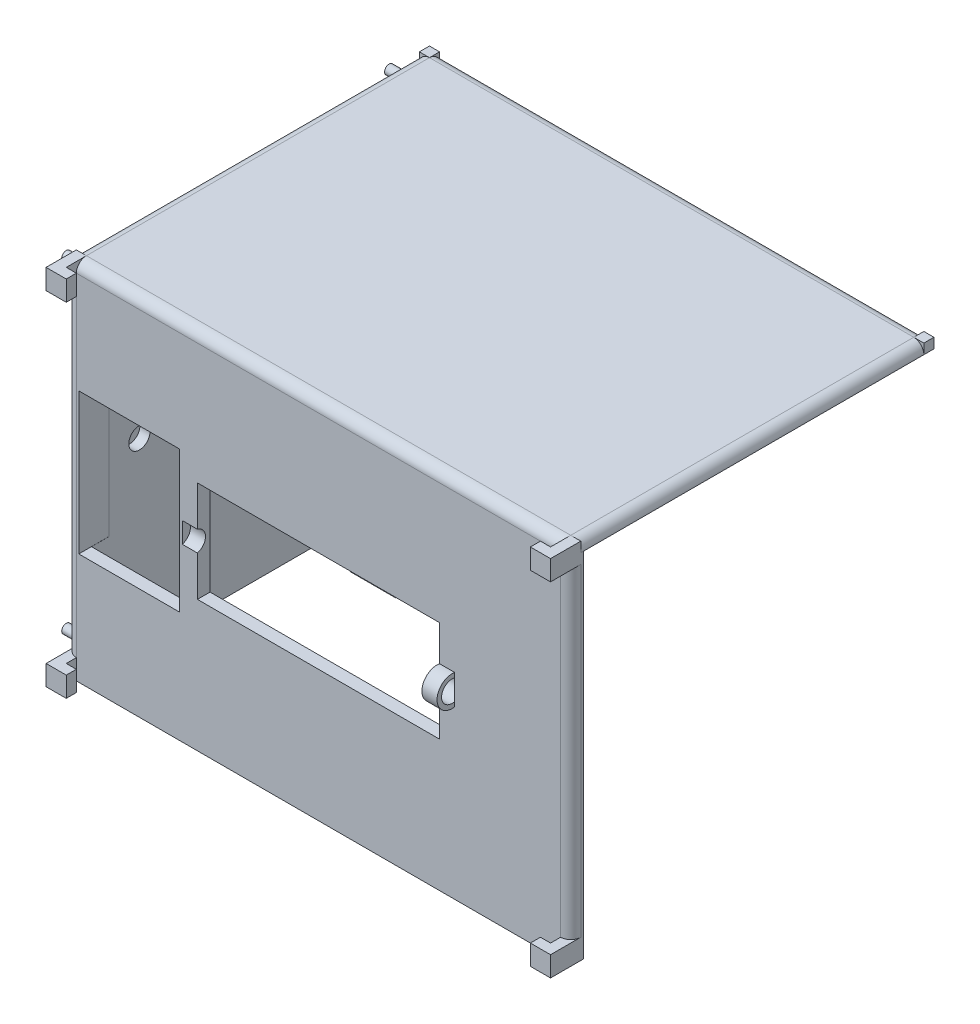
SolidWorks part; units mm, degrees
ref_plane "Front Plane" through (0, 0, 0) normal (0, 0, 1) x (1, 0, 0)
ref_plane "Top Plane" through (0, 0, 0) normal (0, 1, 0) x (1, 0, 0)
ref_plane "Right Plane" through (0, 0, 0) normal (1, 0, 0) x (0, 0, -1)
sketch "Sketch1" plane through (0, 0, 0) normal (0, 1, 0) x (1, 0, 0)
  line L1 (-63.5, -45.72) -> (63.5, -45.72)
  line L2 (-63.5, -45.72) -> (-63.5, 45.72)
  line L3 (-63.5, 45.72) -> (63.5, 45.72)
  line L4 (63.5, -45.72) -> (63.5, 45.72)
  line L5 (-63.5, -45.72) -> (63.5, 45.72) construction
  line L6 (-63.5, 45.72) -> (63.5, -45.72) construction
  point P0 (0, 0)
  dimension "D1" = 91.44
  dimension "D2" = 127
extrude "Boss-Extrude1" add sketch "Sketch1" along normal blind 228.6
sketch "Sketch2" plane through (63.5, 0, 0) normal (1, 0, 0) x (0, 0, -1)
  line L1 (-45.72, 137.16) -> (45.72, 137.16) construction
  line L2 (-45.72, 137.16) -> (-45.72, 228.6) construction
  line L3 (-45.72, 228.6) -> (45.72, 228.6) construction
  line L4 (45.72, 137.16) -> (45.72, 228.6) construction
  line L5 (-45.72, 137.16) -> (45.72, 228.6) construction
  line L6 (-45.72, 228.6) -> (45.72, 137.16) construction
  circle A0 centre (0, 182.88) radius 2.667
  point P0 (0, 182.88)
  dimension "D2" = 5.334
  dimension "D1" = 91.44
sketch "Sketch3" plane through (0, 0, 0) normal (0, -1, 0) x (1, 0, 0)
  line L0 (63.5, 45.72) -> (63.5, -45.72) construction
  line L1 (-60.325, -42.545) -> (60.325, -42.545)
  line L2 (-60.325, -42.545) -> (-60.325, 42.545)
  line L3 (-60.325, 42.545) -> (60.325, 42.545)
  line L4 (60.325, -42.545) -> (60.325, 42.545)
  line L5 (-60.325, -42.545) -> (60.325, 42.545) construction
  line L6 (-60.325, 42.545) -> (60.325, -42.545) construction
  line L7 (-63.5, 45.72) -> (63.5, 45.72) construction
  point P0 (0, 0)
  dimension "D1" = 3.175
  dimension "D2" = 3.175
extrude "Cut-Extrude1" cut sketch "Sketch3" against normal blind 226.06
extrude "Cut-Extrude2" cut sketch "Sketch2" against normal through all contours A0
sketch "Sketch4" plane through (63.5, 0, 0) normal (1, 0, 0) x (0, 0, -1)
  line L3 (-45.72, 228.6) -> (45.72, 228.6) construction
  circle A0 centre (-40.64, 223.52) radius 1.143
  circle A1 centre (40.64, 223.52) radius 1.143
  circle A2 centre (40.64, 142.24) radius 1.143
  circle A3 centre (-40.64, 142.24) radius 1.143
  point P0 (0, 182.88)
  dimension "D7" = 2.286
extrude "Boss-Extrude3" add sketch "Sketch4" along normal blind 5.08
sketch "Sketch5" plane through (60.325, 0, 0) normal (-1, 0, 0) x (0, 0, 1)
  circle A0 centre (0, 182.88) radius 20.32
  dimension "D1" = 40.64
extrude "Cut-Extrude3" cut sketch "Sketch5" against normal blind 1.27
fillet "Fillet1" radius 0.762 1 edges at (61.595, 182.88, 2.667)
fillet "Fillet2" radius 0.762 1 edges at (63.5, 182.88, -2.667)
sketch "Sketch6" plane through (0, 0, 45.72) normal (0, 0, 1) x (1, 0, 0)
  line L0 (0, 0) -> (0, 228.6) construction
  line L1 (-63.5, 228.6) -> (63.5, 228.6) construction
  line L3 (2.7526, 228.6) -> (2.7526, 182.88) construction
  line L4 (-30.48, 170.18) -> (30.48, 170.18)
  line L5 (30.48, 170.18) -> (30.48, 195.58)
  line L6 (-30.48, 170.18) -> (-30.48, 195.58)
  line L7 (30.48, 195.58) -> (-30.48, 195.58)
  line L8 (-30.48, 182.88) -> (30.48, 182.88) construction
  point P10 (0, 170.18)
  dimension "D1" = 45.72
  dimension "D2" = 60.96
  dimension "D3" = 25.4
mirror "Mirror2" about plane through (0, 0, 0) normal (1, 0, 0) of "Cut-Extrude3", "Boss-Extrude3"
fillet "Fillet3" radius 0.762 2 edges at (-61.595, 182.88, -2.667) (-63.5, 182.88, -2.667)
extrude "Cut-Extrude4" cut sketch "Sketch6" against normal through all
fillet "Fillet4" radius 2.54 8 edges at (63.5, 228.6, 0) (0, 228.6, 45.72) (0, 228.6, -45.72) (-63.5, 228.6, 0) (-63.5, 114.3, -45.72) (-63.5, 114.3, 45.72) (63.5, 114.3, 45.72) (63.5, 114.3, -45.72)
sketch "Sketch7" plane through (63.5, 0, 0) normal (1, 0, 0) x (0, 0, -1)
  line L0 (45.72, 226.06) -> (45.72, 0) construction
  line L1 (-42.545, 20.32) -> (42.545, 20.32)
  line L2 (-42.545, 20.32) -> (-42.545, 131.4726)
  line L3 (-42.545, 131.4726) -> (42.545, 131.4726)
  line L4 (42.545, 20.32) -> (42.545, 131.4726)
  line L5 (-42.545, 20.32) -> (42.545, 131.4726) construction
  line L6 (-42.545, 131.4726) -> (42.545, 20.32) construction
  line L7 (-45.72, 0) -> (-45.72, 226.06) construction
  line L8 (-43.18, 0) -> (43.18, 0) construction
  point P0 (0, 75.8963)
  dimension "D1" = 3.175
  dimension "D2" = 3.175
  dimension "D3" = 20.32
extrude "Cut-Extrude5" cut sketch "Sketch7" against normal through all
sketch "Sketch10" plane through (60.325, 0, 0) normal (-1, 0, 0) x (0, 0, 1)
  line L0 (0, 182.88) -> (-30.48, 182.88) construction
  line L1 (-43.18, 226.06) -> (43.18, 226.06) construction
  circle A0 centre (-30.48, 182.88) radius 2.667
  dimension "D2" = 5.334
  dimension "D1" = 30.48
extrude "Cut-Extrude6" cut sketch "Sketch10" against normal blind 2.54
sketch "Sketch11" plane through (60.325, 0, 0) normal (-1, 0, 0) x (0, 0, 1)
  line L0 (-30.48, 182.88) -> (-45.72, 182.88) construction
  dimension "D1" = 15.24
sketch "Sketch12" plane through (0, 0, -45.72) normal (0, 0, -1) x (-1, 0, 0)
  line L1 (-34.8104, 182.8079) -> (-34.8104, 200.5879)
  line L2 (-34.8104, 182.8079) -> (-34.8104, 165.0279)
  line L3 (-34.8104, 165.0279) -> (-60.2104, 165.0279)
  line L4 (-60.2104, 165.0279) -> (-60.2104, 182.8079)
  line L5 (-34.8104, 200.5879) -> (-60.2104, 200.5879)
  line L6 (-60.2104, 200.5879) -> (-60.2104, 182.8079)
  dimension "D1" = 25.4
  dimension "D2" = 17.78
  dimension "D3" = 35.56
extrude "Cut-Extrude7" cut sketch "Sketch12" against normal blind 7.62
sketch "Sketch13" plane through (-60.325, 0, 0) normal (1, 0, 0) x (0, 0, -1)
  line L0 (0, 182.88) -> (-30.48, 182.88) construction
  circle A0 centre (-30.48, 182.88) radius 2.667
  dimension "D2" = 5.334
  dimension "D1" = 30.48
extrude "Cut-Extrude8" cut sketch "Sketch13" against normal blind 2.54
sketch "Sketch15" plane through (-60.325, 0, 0) normal (1, 0, 0) x (0, 0, -1)
  line L0 (-30.48, 182.88) -> (-45.72, 182.88) construction
  dimension "D1" = 15.24
sketch "Sketch16" plane through (0, 0, 45.72) normal (0, 0, 1) x (1, 0, 0)
  line L0 (-60.3464, 182.9342) -> (-60.3464, 200.7142)
  line L1 (-60.3464, 182.9342) -> (-60.3464, 165.1542)
  line L2 (-60.3464, 165.1542) -> (-34.9464, 165.1542)
  line L3 (-34.9464, 165.1542) -> (-34.9464, 200.7142)
  line L4 (-34.9464, 200.7142) -> (-60.3464, 200.7142)
  dimension "D1" = 17.78
  dimension "D2" = 17.78
  dimension "D3" = 25.4
extrude "Cut-Extrude9" cut sketch "Sketch16" against normal blind 7.62
sketch "Sketch17" plane through (-63.5, 0, 0) normal (-1, 0, 0) x (0, 0, 1)
sketch "Sketch20" plane through (0, 226.06, 0) normal (0, -1, 0) x (1, 0, 0)
  line L0 (62.865, -30.48) -> (-4.445, -30.48) construction
  line L1 (62.865, -27.813) -> (62.865, -33.147) construction
  line L2 (-4.445, -30.48) -> (6.985, -30.48) construction
  line L3 (6.985, -34.29) -> (6.985, -26.67)
  line L4 (6.985, -34.29) -> (-4.445, -34.29)
  line L5 (-4.445, -34.29) -> (-4.445, -26.67)
  line L6 (-4.445, -26.67) -> (6.985, -26.67)
  point P8 (6.985, -30.48)
  dimension "D1" = 67.31
  dimension "D2" = 11.43
  dimension "D3" = 7.62
extrude "Boss-Extrude4" add sketch "Sketch20" along normal blind 50.8
sketch "Sketch21" plane through (6.985, 0, 0) normal (1, 0, 0) x (0, 0, -1)
  circle A0 centre (30.48, 182.88) radius 2.667
  dimension "D1" = 5.334
extrude "Cut-Extrude10" cut sketch "Sketch21" against normal blind 12.7
sketch "Sketch23" plane through (6.985, 0, 0) normal (1, 0, 0) x (0, 0, -1)
  line L1 (27.813, 182.88) -> (26.67, 182.88)
  line L2 (26.67, 175.26) -> (26.67, 226.06) construction
  line L3 (26.67, 182.88) -> (26.67, 175.26)
  line L4 (26.67, 175.26) -> (34.29, 175.26)
  line L5 (34.29, 175.26) -> (34.29, 182.88)
  line L6 (34.29, 175.26) -> (34.29, 226.06) construction
  line L7 (34.29, 182.88) -> (27.813, 182.88)
  circle A0 centre (30.48, 182.88) radius 2.667 construction
extrude "Cut-Extrude11" cut sketch "Sketch23" against normal blind 12.7
sketch "Sketch24" plane through (30.48, 0, 0) normal (-1, 0, 0) x (0, 0, 1)
  line L0 (-30.48, 182.88) -> (-46.355, 182.88) construction
  circle A0 centre (-46.355, 182.88) radius 3.81
  dimension "D2" = 7.62
  dimension "D1" = 15.875
extrude "Boss-Extrude5" add sketch "Sketch24" against normal blind 3.81
sketch "Sketch25" plane through (30.48, 0, 0) normal (-1, 0, 0) x (0, 0, 1)
  circle A0 centre (-46.355, 182.88) radius 2.667
  dimension "D1" = 5.334
extrude "Cut-Extrude12" cut sketch "Sketch25" against normal blind 3.81
mirror "Mirror3" about plane through (0, 0, 0) normal (0, 0, 1) of "Boss-Extrude4", "Cut-Extrude10", "Cut-Extrude12", "Boss-Extrude5"
sketch "Sketch26" plane through (6.985, 0, 0) normal (1, 0, 0) x (0, 0, -1)
  line L0 (-27.813, 182.88) -> (-26.67, 182.88)
  line L1 (-26.67, 175.26) -> (-26.67, 226.06) construction
  line L2 (-26.67, 182.88) -> (-26.67, 175.26)
  line L3 (-26.67, 175.26) -> (-34.29, 175.26)
  line L4 (-34.29, 175.26) -> (-34.29, 182.88)
  line L5 (-30.48, 182.88) -> (-45.72, 182.88) construction
  line L6 (-34.29, 175.26) -> (-34.29, 226.06) construction
  line L7 (-34.29, 182.88) -> (-27.813, 182.88)
  circle A0 centre (-30.48, 182.88) radius 2.667 construction
extrude "Cut-Extrude13" cut sketch "Sketch26" against normal blind 12.7
sketch "Sketch27" plane through (30.48, 0, 0) normal (-1, 0, 0) x (0, 0, 1)
  circle A0 centre (-46.355, 182.88) radius 2.667
extrude "Cut-Extrude14" cut sketch "Sketch27" along normal blind 64.77 contours A0
sketch "Sketch29" plane through (30.48, 0, 0) normal (-1, 0, 0) x (0, 0, 1)
  circle A0 centre (46.355, 182.88) radius 2.667
extrude "Cut-Extrude15" cut sketch "Sketch29" along normal blind 64.77
sketch "Sketch31" plane through (0, 0, 0) normal (1, 0, 0) x (0, 0, -1)
  circle A0 centre (-46.355, 182.88) radius 12.7 construction
  dimension "D1" = 25.4
fillet "Fillet6" radius 50.8 1 edges at (1.27, 182.88, 34.29)
fillet "Fillet7" radius 50.8 1 edges at (1.27, 182.88, -34.29)
sketch "Sketch33" plane through (0, 228.6, 0) normal (0, 1, 0) x (1, 0, 0)
  line L0 (63.5, 43.18) -> (63.5, 50.8)
  line L1 (63.5, 50.8) -> (58.42, 50.8)
  line L2 (58.42, 50.8) -> (58.42, 48.26)
  line L3 (58.42, 48.26) -> (60.96, 48.26)
  line L4 (60.96, 48.26) -> (60.96, 43.18)
  line L5 (60.96, 43.18) -> (63.5, 43.18)
extrude "Boss-Extrude6" add sketch "Sketch33" against normal blind 5.08
mirror "Mirror4" about plane through (0, 0, 0) normal (1, 0, 0) of "Boss-Extrude6"
ref_plane "Plane1" through (0, 182.88, 0) normal (0, 1, 0) x (1, 0, 0)
mirror "Mirror5" about plane through (0, 182.88, 0) normal (0, 1, 0) of "Mirror4", "Boss-Extrude6"
mirror "Mirror6" about plane through (0, 0, 0) normal (0, 0, 1) of "Mirror5", "Boss-Extrude6", "Mirror4"
sketch "Sketch35" plane through (0, 0, 0) normal (0, 0, 1) x (1, 0, 0)
  line L0 (-63.5, 137.16) -> (63.5, 137.16)
  line L1 (63.5, 137.16) -> (63.5, 0)
  line L2 (63.5, 0) -> (-63.5, 0)
  line L3 (-63.5, 0) -> (-63.5, 137.16)
extrude "Cut-Extrude16" cut sketch "Sketch35" against normal mid plane 104.14
sketch "Sketch39" plane through (63.5, 0, 0) normal (1, 0, 0) x (0, 0, -1)
  line L0 (42.545, 137.16) -> (42.545, 226.06)
  line L1 (42.545, 226.06) -> (-42.545, 226.06)
  line L2 (-42.545, 226.06) -> (-42.545, 137.16)
  line L3 (-42.545, 137.16) -> (42.545, 137.16)
extrude "Cut-Extrude20" cut sketch "Sketch39" against normal mid plane 104.14
sketch "Sketch41" plane through (0, 0, -45.72) normal (0, 0, -1) x (-1, 0, 0)
  line L0 (60.325, 137.16) -> (60.325, 226.06)
  line L1 (60.325, 226.06) -> (-63.5, 226.06)
  line L2 (-63.5, 226.06) -> (-63.5, 137.16)
  line L3 (-63.5, 137.16) -> (60.325, 137.16)
extrude "Cut-Extrude21" cut sketch "Sketch41" against normal mid plane 104.14
sketch "Sketch42" plane through (0, 0, 0) normal (0, 1, 0) x (1, 0, 0)
  line L0 (63.5, 45.72) -> (-63.5, 45.72)
  line L1 (63.5, 43.18) -> (63.5, 50.8) construction
  line L2 (-63.5, 43.18) -> (-63.5, 50.8) construction
  line L3 (-63.5, 45.72) -> (-63.5, 50.8)
  line L4 (-63.5, 50.8) -> (63.5, 50.8)
  line L5 (63.5, 50.8) -> (63.5, 45.72)
extrude "Cut-Extrude22" cut sketch "Sketch42" along normal blind 236.22
